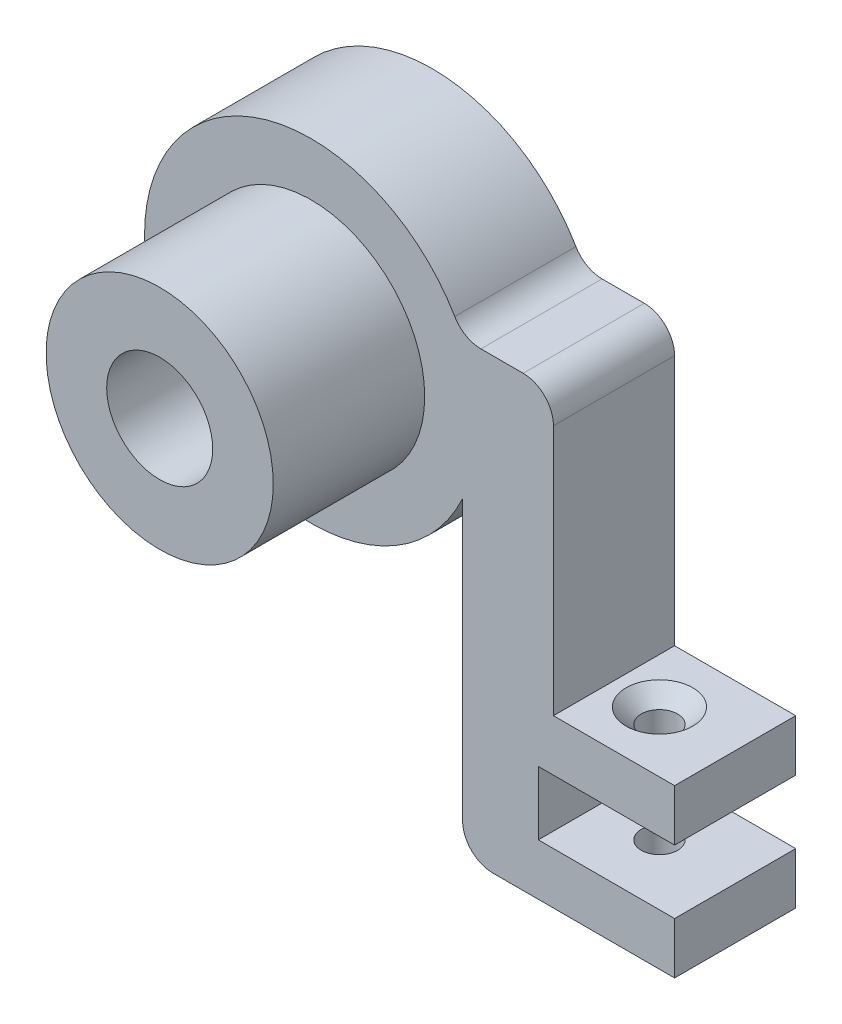
SolidWorks part; units mm, degrees
ref_plane "Plan de face" through (0, 0, 0) normal (0, 0, 1) x (1, 0, 0)
ref_plane "Plan de dessus" through (0, 0, 0) normal (0, 1, 0) x (1, 0, 0)
ref_plane "Plan de droite" through (0, 0, 0) normal (1, 0, 0) x (0, 0, -1)
sketch "Esquisse1" plane through (0, 0, 0) normal (0, 0, 1) x (1, 0, 0)
  line L1 (0, 0) -> (35, 0) construction
  line L2 (0, 0) -> (0, -36) construction
  line L3 (0, -36) -> (35, -36) construction
  line L4 (35, 0) -> (35, -36) construction
  line L5 (21, -6.4174) -> (27, -6.4174)
  line L7 (27, -6.4174) -> (27, -25)
  line L8 (35, -28.4) -> (35, -25)
  line L9 (35, -36) -> (21, -36)
  line L10 (35, -36) -> (35, -32.6)
  line L11 (35, -25) -> (27, -25)
  line L14 (21, -36) -> (21, -15.5826)
  line L17 (35, -32.6) -> (26, -32.6)
  line L19 (35, -28.4) -> (26, -28.4)
  line L20 (26, -32.6) -> (26, -28.4)
  line L21 (21, -6.4174) -> (21, -15.5826) construction
  arc A0 (21, -6.4174) -> (21, -15.5826) centre (11, -11) ccw
  point P6 (21, -11)
  point P20 (26, -30.5)
  dimension "D3" = 22
  dimension "D1" = 35
  dimension "D2" = 36
  dimension "D4" = 11
  dimension "D5" = 11
  dimension "D6" = 11
  dimension "D8" = 9
  dimension "D9" = 4.2
  dimension "D10" = 5.5
  dimension "D11" = 8
  dimension "D7" = 21
extrude "Boss.-Extru.1" add sketch "Esquisse1" along normal blind 8
sketch "Esquisse2" plane through (0, -25, 0) normal (0, 1, 0) x (1, 0, 0)
  line L0 (27, -8) -> (27, 0) construction
  line L1 (35, -8) -> (27, -8) construction
  circle A0 centre (30, -4) radius 1
  dimension "D1" = 2
  dimension "D2" = 3
  dimension "D3" = 4
extrude "Enlèv. mat.-Extru.1" cut sketch "Esquisse2" against normal up to surface (11 mm away) up to face at (28, -36, 4)
hole_wizard "Fraisage pour vis à tête fraisée M21" positions "Esquisse3" profile "Esquisse4" countersink size "M2" standard "ISO"
sketch "Esquisse3" plane through (0, -25, 0) normal (0, 1, 0) x (1, 0, 0)
  point P0 (30, -4)
sketch "Esquisse4" plane through (30, -25, 4) normal (1, 0, 0) x (0, 0, 1)
  line L0 (0, 0) -> (0, 11.721)
  line L1 (0, 11.721) -> (1.2, 11)
  line L2 (1.2, 11) -> (1.2, 1)
  line L3 (1.2, 1) -> (2.2, 0)
  line L5 (2.2, 0) -> (0, 0)
  line L6 (-1.2, 1) -> (-2.2, 0) construction
  line L10 (0, 11.721) -> (-1.2, 11) construction
  line L11 (0, -6.35) -> (0, 107.95) construction
  dimension "Diamètre du perçage" = 2.4
  dimension "Profondeur du perçage" = 11
  dimension "Diamètre du fraisage entrant" = 4.4
  dimension "Angle du fraisage entrant" = 90
  dimension "Angle de pointe" = 118
fillet "Congé1" radius 2 3 edges at (21, -36, 4) (21, -6.4174, 4) (27, -6.4174, 4)
sketch "Esquisse5" plane through (0, 0, 8) normal (0, 0, 1) x (1, 0, 0)
  circle A0 centre (11, -11) radius 7.5
  dimension "D1" = 15
extrude "Boss.-Extru.2" add sketch "Esquisse5" along normal blind 10
sketch "Esquisse6" plane through (0, 0, 0) normal (0, 0, -1) x (-1, 0, 0)
  line L0 (-11, -3.5) -> (-11, -18.5) construction
  line L1 (0, -4.0566) -> (0, -19.2348) construction
  line L2 (-19.6078, 0) -> (-3.8534, 0) construction
  circle A0 centre (-11, -3.5) radius 1
  circle A1 centre (-11, -18.5) radius 1
  arc A2 (-21, -15.5826) -> (-20.4856, -5.4301) centre (-11, -11) ccw construction
  circle A3 centre (-11, -11) radius 3.5 construction
  point P8 (-11, -11)
  dimension "D2" = 2
  dimension "D3" = 2
  dimension "D5" = 7
  dimension "D1" = 11
  dimension "D4" = 11
  dimension "D6" = 15
extrude "Enlèv. mat.-Extru.2" cut sketch "Esquisse6" against normal offset from surface (6 mm away) 2 up to face at (18.5, -11, 8)
sketch "Esquisse8" plane through (0, 0, 0) normal (0, 0, -1) x (-1, 0, 0)
  circle A0 centre (-11, -11) radius 3.5
  dimension "D1" = 7
extrude "Enlèv. mat.-Extru.3" cut sketch "Esquisse8" against normal up to surface (18 mm away) up to face at (18.5, -11, 18)
equation "\"D4@Esquisse1\"=\"D3@Esquisse1\"/2"
equation "\"D5@Esquisse1\"=\"D3@Esquisse1\"/2"
equation "\"D10@Esquisse1\"=\"D6@Esquisse1\"/2"
